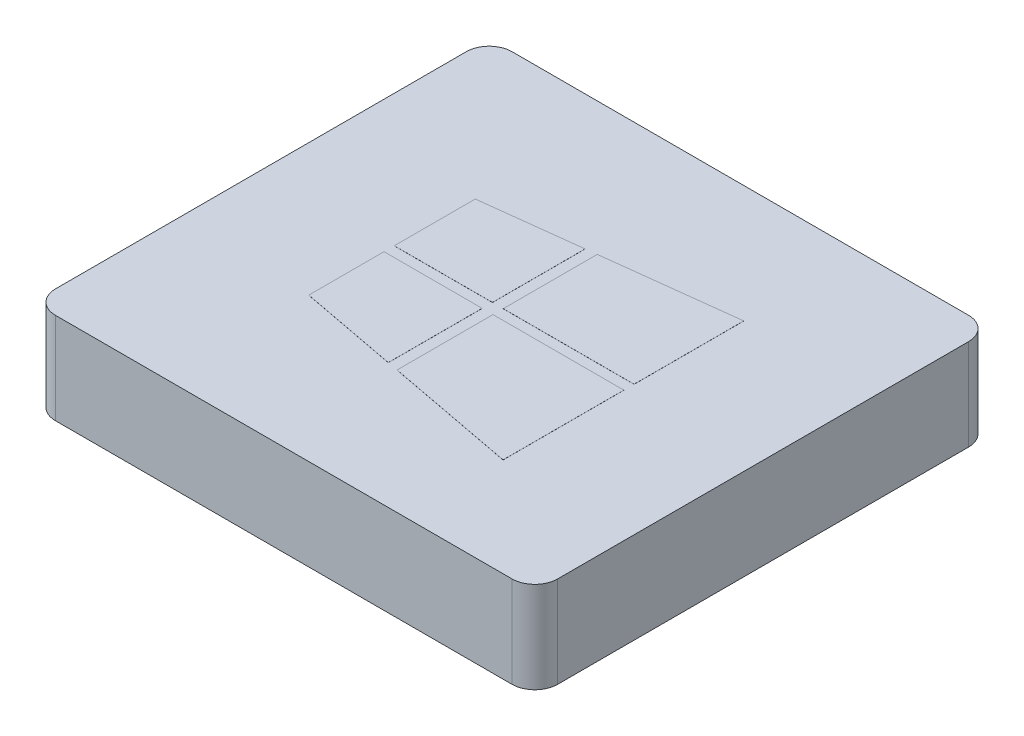
SolidWorks part; units mm, degrees
ref_plane "Front Plane" through (0, 0, 0) normal (0, 0, 1) x (1, 0, 0)
ref_plane "Top Plane" through (0, 0, 0) normal (0, 1, 0) x (1, 0, 0)
ref_plane "Right Plane" through (0, 0, 0) normal (1, 0, 0) x (0, 0, -1)
sketch "Sketch1" plane through (0, 0, 0) normal (0, 1, 0) x (1, 0, 0)
  line L0 (0, 0) -> (13.97, 0)
  line L1 (13.97, 0) -> (13.97, 12.7)
  line L2 (13.97, 12.7) -> (0, 12.7)
  line L3 (0, 12.7) -> (0, 0)
  dimension "D1" = 13.97
  dimension "D2" = 12.7
extrude "Boss-Extrude1" add sketch "Sketch1" along normal blind 2.54
fillet "Fillet1" radius 0.635 4 edges at (0, 1.27, -12.7) (13.97, 1.27, -12.7) (13.97, 1.27, 0) (0, 1.27, 0)
shell "Shell1" thickness 0.635 removed face at (6.985, 0, -6.35)
sketch "Sketch2" plane through (0, 1.905, 0) normal (0, -1, 0) x (-1, 0, 0)
  line L0 (-0.635, 6.35) -> (-13.335, 6.35) construction
  line L1 (-0.635, 12.065) -> (-0.635, 0.635) construction
  line L2 (-13.335, 0.635) -> (-13.335, 12.065) construction
  line L3 (-6.985, 0.635) -> (-6.985, 12.065) construction
  line L4 (-0.635, 0.635) -> (-13.335, 0.635) construction
  line L5 (-13.335, 12.065) -> (-0.635, 12.065) construction
  circle A0 centre (-6.985, 6.35) radius 2.54
  dimension "D1" = 5.08
extrude "Boss-Extrude2" add sketch "Sketch2" along normal up to surface (1.905 mm away) up to face at (6.985, 0, -6.35)
sketch "Sketch5" plane through (0, 2.54, 0) normal (0, 1, 0) x (1, 0, 0)
  line L0 (3.6758, 8.6369) -> (6.4058, 8.9634)
  line L1 (6.4058, 8.9634) -> (6.4058, 6.385)
  line L2 (6.4058, 6.385) -> (3.6758, 6.385)
  line L3 (3.6758, 6.385) -> (3.6758, 8.6369)
  line L4 (3.6758, 6.0997) -> (3.6758, 4.0066)
  line L5 (3.6758, 4.0066) -> (6.4058, 3.4885)
  line L6 (6.4058, 3.4885) -> (6.4058, 6.0997)
  line L7 (6.4058, 6.0997) -> (3.6758, 6.0997)
  line L8 (6.7065, 8.9993) -> (6.7065, 6.385)
  line L9 (6.7065, 6.385) -> (10.3458, 6.385)
  line L10 (10.3458, 6.385) -> (10.3458, 9.4346)
  line L11 (10.3458, 9.4346) -> (6.7065, 8.9993)
  line L12 (6.7065, 6.0997) -> (6.7065, 3.4314)
  line L13 (6.7065, 3.4314) -> (10.3458, 2.7407)
  line L14 (10.3458, 2.7407) -> (10.3458, 6.0997)
  line L15 (10.3458, 6.0997) -> (6.7065, 6.0997)
  line L16 (0, 12.065) -> (0, 0.635) construction
  line L17 (13.335, 12.7) -> (0.635, 12.7) construction
  dimension "D1" = 2.73
  dimension "D2" = 2.2518
  dimension "D3" = 0.2853
  dimension "D4" = 3.6393
  dimension "D5" = 0.3008
  dimension "D6" = 3.6652
  dimension "D7" = 2.0931
  dimension "D8" = 3.6758
  dimension "D9" = 6.315
  dimension "D10" = 2.6683
extrude "Boss-Extrude4" add sketch "Sketch5" along normal blind 0.0025
